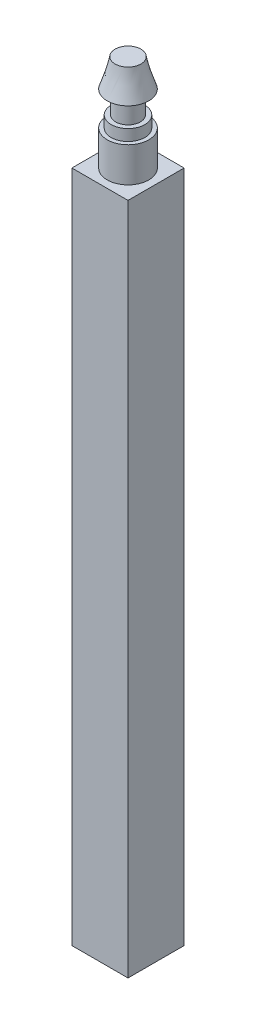
SolidWorks part; units mm, degrees
ref_plane "Front Plane" through (0, 0, 0) normal (0, 0, 1) x (1, 0, 0)
ref_plane "Top Plane" through (0, 0, 0) normal (0, 1, 0) x (1, 0, 0)
ref_plane "Right Plane" through (0, 0, 0) normal (1, 0, 0) x (0, 0, -1)
sketch "Sketch1" plane through (0, 0, 0) normal (0, 1, 0) x (1, 0, 0)
  circle A0 centre (0, 0) radius 1.85
  dimension "D1" = 3.7
extrude "Boss-Extrude1" add sketch "Sketch1" along normal blind 3.1
sketch "Sketch2" plane through (0, 3.1, 0) normal (0, 1, 0) x (1, 0, 0)
  circle A0 centre (0, 0) radius 1.5
  dimension "D1" = 3
extrude "Boss-Extrude2" add sketch "Sketch2" along normal blind 1
sketch "Sketch3" plane through (0, 4.1, 0) normal (0, 1, 0) x (1, 0, 0)
  circle A0 centre (0, 0) radius 1.1
  dimension "D1" = 2.2
extrude "Boss-Extrude3" add sketch "Sketch3" along normal blind 2
sketch "Sketch4" plane through (0, 6.1, 0) normal (0, 1, 0) x (1, 0, 0)
  circle A0 centre (0, 0) radius 1.85
  dimension "D1" = 3.7
ref_plane "Plane1" through (0, 8.6, 0) normal (0, 1, 0) x (1, 0, 0)
sketch "Sketch5" plane through (0, 8.6, 0) normal (0, 1, 0) x (1, 0, 0)
  circle A0 centre (0, 0) radius 1.15
  dimension "D1" = 2.3
loft "Loft1" add profiles "Sketch4", "Sketch5" connector at (0, 6.1, 1.85) connector at (0.6205, 8.6, 0.9683)
sketch "Sketch6" plane through (0, 0, 0) normal (0, -1, 0) x (1, 0, 0)
  line L1 (-2.5, 2.5) -> (2.5, 2.5)
  line L2 (-2.5, 2.5) -> (-2.5, -2.5)
  line L3 (-2.5, -2.5) -> (2.5, -2.5)
  line L4 (2.5, 2.5) -> (2.5, -2.5)
  line L5 (-2.5, 2.5) -> (2.5, -2.5) construction
  line L6 (-2.5, -2.5) -> (2.5, 2.5) construction
  point P0 (0, 0)
  dimension "D1" = 5
  dimension "D2" = 5
extrude "Boss-Extrude4" add sketch "Sketch6" along normal blind 60
sketch "Sketch7" plane through (0, -60, 0) normal (0, -1, 0) x (1, 0, 0)
  circle A0 centre (0, 0) radius 1
  dimension "D1" = 2
extrude "Cut-Extrude1" cut sketch "Sketch7" against normal blind 24
